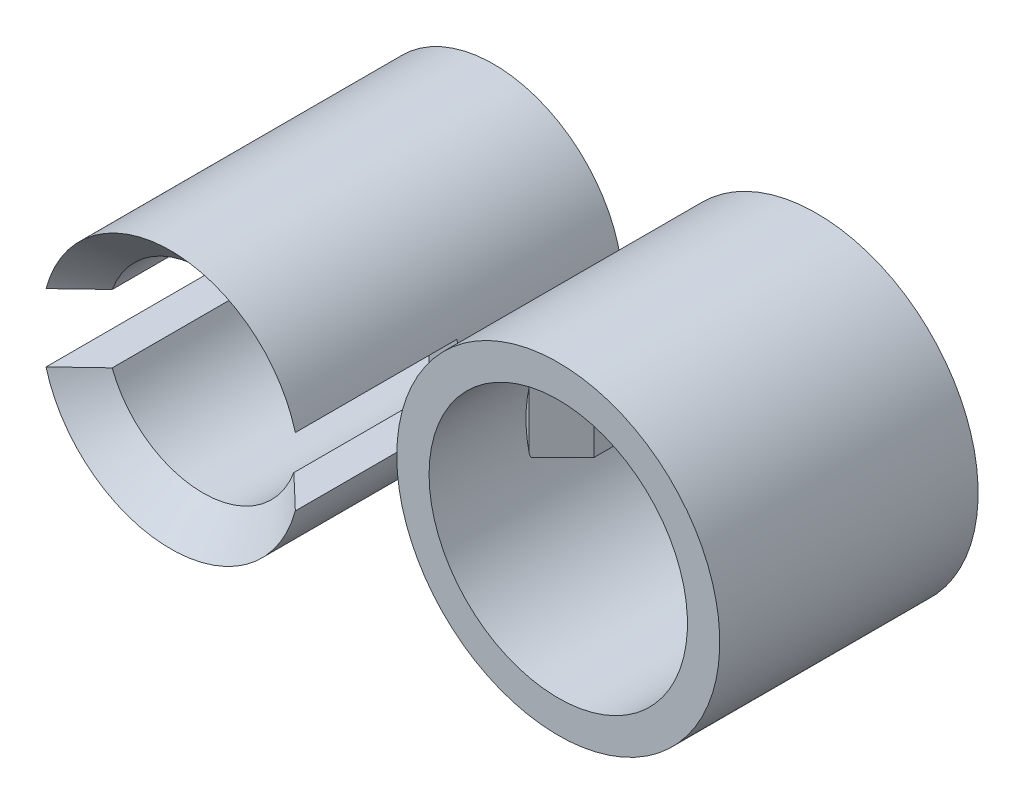
SolidWorks part; units mm, degrees
ref_plane "Front Plane" through (0, 0, 0) normal (0, 0, 1) x (1, 0, 0)
ref_plane "Top Plane" through (0, 0, 0) normal (0, 1, 0) x (1, 0, 0)
ref_plane "Right Plane" through (0, 0, 0) normal (1, 0, 0) x (0, 0, -1)
sketch "Sketch1" plane through (0, 0, 0) normal (0, 0, 1) x (1, 0, 0)
  circle A0 centre (0, 0) radius 3
  circle A1 centre (0, 0) radius 4
  dimension "D1" = 6
  dimension "D2" = 1
extrude "Boss-Extrude1" add sketch "Sketch1" along normal blind 10
sketch "Sketch2" plane through (0, 0, 10) normal (0, 0, 1) x (1, 0, 0)
  line L1 (-4, -1.05) -> (4, -1.05)
  line L2 (-4, -1.05) -> (-4, 1.05)
  line L3 (-4, 1.05) -> (4, 1.05)
  line L4 (4, -1.05) -> (4, 1.05)
  line L5 (-4, -1.05) -> (4, 1.05) construction
  line L6 (-4, 1.05) -> (4, -1.05) construction
  circle A0 centre (0, 0) radius 4 construction
  point P0 (0, 0)
  dimension "D1" = 2.1
extrude "Cut-Extrude1" cut sketch "Sketch2" against normal blind 5
sketch "Sketch3" plane through (0, 0, 0) normal (0, 0, -1) x (-1, 0, 0)
  circle A0 centre (-10, 0) radius 4
  circle A1 centre (-10, 0) radius 5
  circle A2 centre (0, 0) radius 3 construction
  dimension "D1" = 8
  dimension "D2" = 1
  dimension "D3" = 10
extrude "Boss-Extrude2" add sketch "Sketch3" against normal blind 8 separate body
sketch "Sketch4" plane through (0, 0, 0) normal (0, 0, -1) x (-1, 0, 0)
  line L1 (-5.101, -1) -> (-14.899, -1)
  line L2 (-5.101, -1) -> (-5.101, 1)
  line L3 (-5.101, 1) -> (-14.899, 1)
  line L4 (-14.899, -1) -> (-14.899, 1)
  line L5 (-5.101, -1) -> (-14.899, 1) construction
  line L6 (-5.101, 1) -> (-14.899, -1) construction
  line L7 (-7.101, -1) -> (-12.899, -1)
  line L8 (-7.101, -1) -> (-7.101, 1)
  line L9 (-7.101, 1) -> (-12.899, 1)
  line L10 (-12.899, -1) -> (-12.899, 1)
  line L11 (-7.101, -1) -> (-12.899, 1) construction
  line L12 (-7.101, 1) -> (-12.899, -1) construction
  circle A0 centre (-10, 0) radius 5 construction
  point P0 (-10, 0)
  point P8 (-10, 0)
  circle M3 centre (-10, 0) radius 4
  dimension "D1" = 2
  dimension "D2" = 2
extrude "Boss-Extrude3" add sketch "Sketch4" against normal blind 5 contours L1 L10 L3 M3 | L8 L1 L3 M3 region at (6.5709, 0, 0) region at (13.4291, 0, 0)
chamfer "Chamfer1" distance 1 angle 45 2 edges at (12.899, 0, 5) (7.101, 0, 5)
chamfer "Chamfer2" distance 1 angle 45 2 edges at (0, -3, 10) (0, 3, 10)
